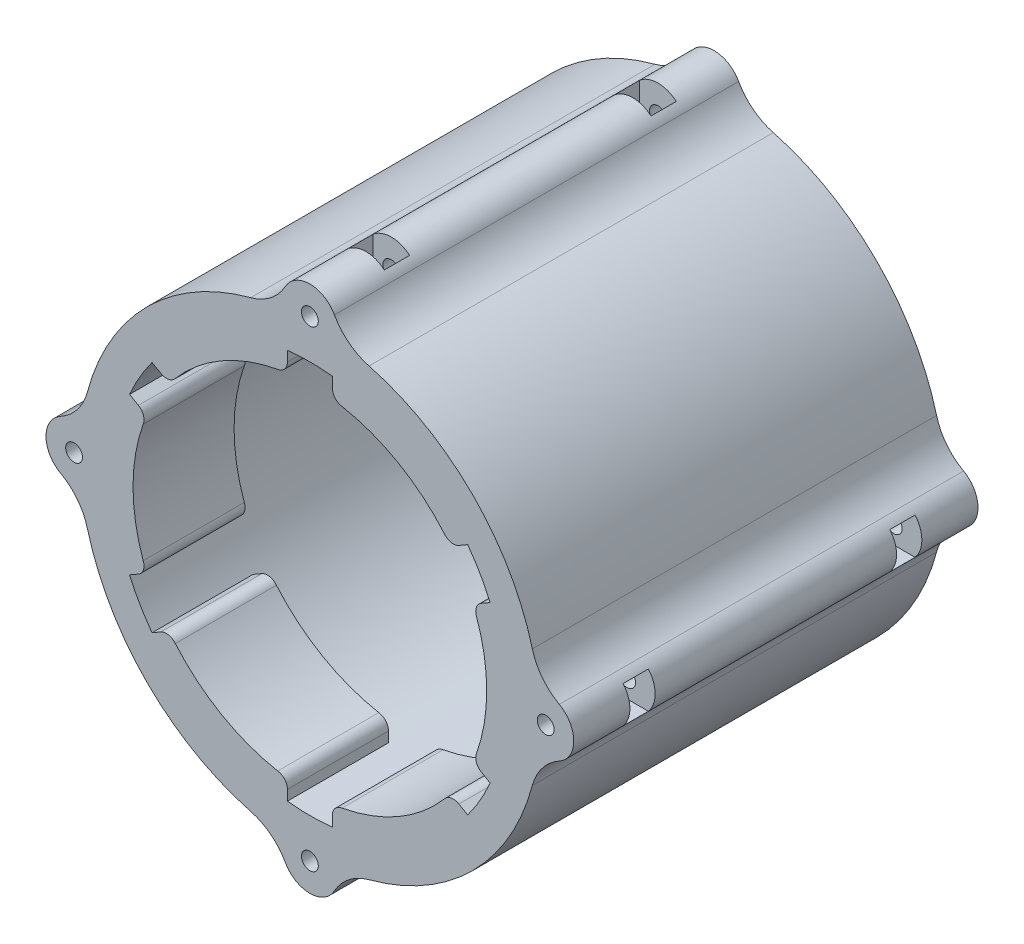
SolidWorks part; units mm, degrees
ref_plane "Ön Düzlem" through (0, 0, 0) normal (0, 0, 1) x (1, 0, 0)
ref_plane "Üst Düzlem" through (0, 0, 0) normal (0, 1, 0) x (1, 0, 0)
ref_plane "Sağ Düzlem" through (0, 0, 0) normal (1, 0, 0) x (0, 0, -1)
sketch "Çizim1" plane through (0, 0, 0) normal (0, 0, 1) x (1, 0, 0)
  circle A0 centre (0, 0) radius 35
  arc A1 (-39.6218, -10.5408) -> (-10.5408, -39.6218) centre (0, 0) ccw
  circle A6 centre (-42, 0) radius 1.5
  arc A7 (-44.4286, 4.3706) -> (-44.4286, -4.3706) centre (-42, 0) ccw
  circle A8 centre (0, 0) radius 41 construction
  arc A9 (-39.6218, -10.5408) -> (-44.4286, -4.3706) centre (-49.2857, -13.1118) ccw
  arc A10 (-39.6218, 10.5408) -> (-44.4286, 4.3706) centre (-49.2857, 13.1118) cw
  circle A11 centre (0, 42) radius 1.5
  arc A12 (4.3706, 44.4286) -> (-4.3706, 44.4286) centre (0, 42) ccw
  arc A13 (-10.5408, 39.6218) -> (-4.3706, 44.4286) centre (-13.1118, 49.2857) ccw
  arc A14 (10.5408, 39.6218) -> (4.3706, 44.4286) centre (13.1118, 49.2857) cw
  circle A15 centre (42, 0) radius 1.5
  arc A16 (44.4286, -4.3706) -> (44.4286, 4.3706) centre (42, 0) ccw
  arc A17 (39.6218, 10.5408) -> (44.4286, 4.3706) centre (49.2857, 13.1118) ccw
  arc A18 (39.6218, -10.5408) -> (44.4286, -4.3706) centre (49.2857, -13.1118) cw
  circle A19 centre (0, -42) radius 1.5
  arc A20 (-4.3706, -44.4286) -> (4.3706, -44.4286) centre (0, -42) ccw
  arc A21 (10.5408, -39.6218) -> (4.3706, -44.4286) centre (13.1118, -49.2857) ccw
  arc A22 (-10.5408, -39.6218) -> (-4.3706, -44.4286) centre (-13.1118, -49.2857) cw
  arc A23 (-10.5408, 39.6218) -> (-39.6218, 10.5408) centre (0, 0) ccw
  arc A24 (39.6218, 10.5408) -> (10.5408, 39.6218) centre (0, 0) ccw
  arc A25 (10.5408, -39.6218) -> (39.6218, -10.5408) centre (0, 0) ccw
  point P16 (0, 0)
  point P41 (0, 0)
  dimension "D1" = 70
  dimension "D3" = 5
  dimension "D4" = 3
  dimension "D5" = 42
  dimension "D6" = 10
  dimension "D2" = 6
  dimension "D7" = 4
extrude "Yükseklik-Ekstrüzyon1" add sketch "Çizim1" along normal blind 72
sketch "Çizim2" plane through (0, 0, 72) normal (0, 0, 1) x (1, 0, 0)
  line L0 (-4, 34.7707) -> (-4, 32.9563)
  line L1 (4, 34.7707) -> (4, 32.9563)
  line L2 (28.1123, 20.8494) -> (26.541, 19.9422)
  line L3 (32.1123, 13.9212) -> (30.541, 13.014)
  line L4 (32.1123, -13.9212) -> (30.541, -13.014)
  line L5 (28.1123, -20.8494) -> (26.541, -19.9422)
  line L6 (4, -34.7707) -> (4, -32.9563)
  line L7 (-4, -34.7707) -> (-4, -32.9563)
  line L8 (-28.1123, -20.8494) -> (-26.541, -19.9422)
  line L9 (-32.1123, -13.9212) -> (-30.541, -13.014)
  line L10 (-32.1123, 13.9212) -> (-30.541, 13.014)
  line L11 (-28.1123, 20.8494) -> (-26.541, 19.9422)
  arc A0 (26.541, 19.9422) -> (23.9615, 20.4474) centre (25.541, 21.6743) cw
  arc A3 (-4, 34.7707) -> (-28.1123, 20.8494) centre (0, 0) ccw
  arc A5 (4, 32.9563) -> (5.7273, 30.975) centre (6, 32.9563) ccw
  arc A6 (-4, 32.9563) -> (-5.7273, 30.975) centre (-6, 32.9563) cw
  arc A19 (-5.7273, 30.975) -> (-23.9615, 20.4474) centre (0, 0) ccw
  arc A20 (30.541, 13.014) -> (29.6887, 10.5275) centre (31.541, 11.282) ccw
  arc A21 (30.541, -13.014) -> (29.6887, -10.5275) centre (31.541, -11.282) cw
  arc A22 (26.541, -19.9422) -> (23.9615, -20.4474) centre (25.541, -21.6743) ccw
  arc A23 (4, -32.9563) -> (5.7273, -30.975) centre (6, -32.9563) cw
  arc A24 (-4, -32.9563) -> (-5.7273, -30.975) centre (-6, -32.9563) ccw
  arc A25 (-26.541, -19.9422) -> (-23.9615, -20.4474) centre (-25.541, -21.6743) cw
  arc A26 (-30.541, -13.014) -> (-29.6887, -10.5275) centre (-31.541, -11.282) ccw
  arc A27 (-30.541, 13.014) -> (-29.6887, 10.5275) centre (-31.541, 11.282) cw
  arc A28 (-26.541, 19.9422) -> (-23.9615, 20.4474) centre (-25.541, 21.6743) ccw
  circle A29 centre (0, 0) radius 35 construction
  circle A30 centre (0, 0) radius 31.5 construction
  arc A31 (28.1123, 20.8494) -> (4, 34.7707) centre (0, 0) ccw
  arc A32 (23.9615, 20.4474) -> (5.7273, 30.975) centre (0, 0) ccw
  arc A33 (29.6887, -10.5275) -> (29.6887, 10.5275) centre (0, 0) ccw
  arc A34 (32.1123, -13.9212) -> (32.1123, 13.9212) centre (0, 0) ccw
  arc A35 (5.7273, -30.975) -> (23.9615, -20.4474) centre (0, 0) ccw
  arc A36 (4, -34.7707) -> (28.1123, -20.8494) centre (0, 0) ccw
  arc A37 (-23.9615, -20.4474) -> (-5.7273, -30.975) centre (0, 0) ccw
  arc A38 (-28.1123, -20.8494) -> (-4, -34.7707) centre (0, 0) ccw
  arc A39 (-29.6887, 10.5275) -> (-29.6887, -10.5275) centre (0, 0) ccw
  arc A40 (-32.1123, 13.9212) -> (-32.1123, -13.9212) centre (0, 0) ccw
  point P9 (36.0972, 15.5128)
  point P13 (0, 0)
  point P55 (0, 0)
  dimension "D2" = 3.5
  dimension "D4" = 2
  dimension "D1" = 70
  dimension "D6" = 1.8144
  dimension "D3" = 4
  dimension "D5" = 4
  dimension "D7" = 1.8144
  dimension "D8" = 6
extrude "Yükseklik-Ekstrüzyon2" add sketch "Çizim2" against normal blind 18
ref_plane "Düzlem1" through (0, 0, 10) normal (0, 0, -1) x (-1, 0, 0)
sketch "Çizim3" plane through (0, 0, 10) normal (0, 0, -1) x (-1, 0, 0)
  line L0 (-3.262, -42) -> (-3.262, -48)
  line L1 (3.262, -42) -> (1.631, -39.175)
  line L2 (1.631, -39.175) -> (-1.631, -39.175)
  line L3 (-1.631, -39.175) -> (-3.262, -42)
  line L7 (3.262, -42) -> (3.262, -48)
  line L8 (3.262, -48) -> (-3.262, -48)
  line L9 (-2.4465, -43.4125) -> (-1.631, -44.825) [skipped]
  line L10 (0, -44.825) -> (1.631, -44.825) [skipped]
  line L11 (2.4465, -43.4125) -> (3.262, -42) [skipped]
  circle A0 centre (0, -42) radius 2.825 construction
  dimension "D1" = 3.262
  dimension "D2" = 6
  dimension "D3" = 6
  dimension "D4" = 3.262
  dimension "D5" = 3.262
extrude "Kes-Ekstrüzyon1" cut sketch "Çizim3" against normal blind 4.5
pattern_circular "Dairesel Kaplama1" count 4 every 90 about axis through (0, 0, 0) along (0, 0, 1) of "Kes-Ekstrüzyon1"
ref_plane "Düzlem2" through (0, 0, 36) normal (0, 0, -1) x (-1, 0, 0)
mirror "Aynalama1" about plane through (0, 0, 36) normal (0, 0, -1) of "Dairesel Kaplama1"
